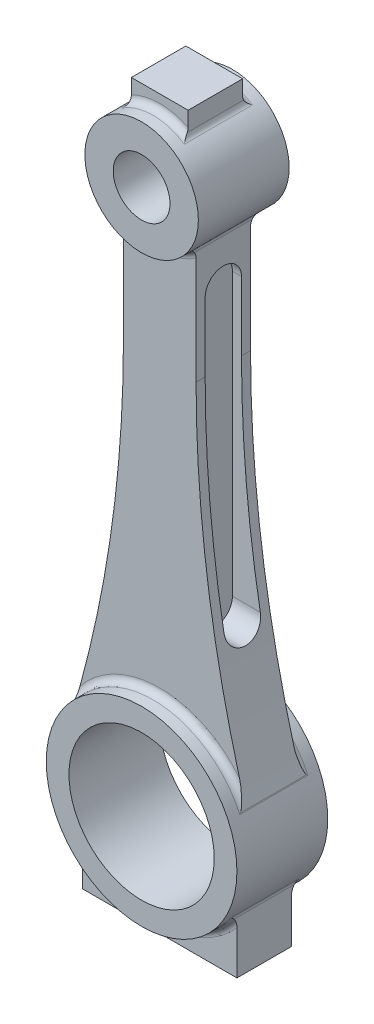
SolidWorks part; units mm, degrees
material "Ti-8Mn annealed sheet (SS)"
ref_plane "Front Plane" through (0, 0, 0) normal (0, 0, 1) x (1, 0, 0)
ref_plane "Top Plane" through (0, 0, 0) normal (0, 1, 0) x (1, 0, 0)
ref_plane "Right Plane" through (0, 0, 0) normal (1, 0, 0) x (0, 0, -1)
sketch "Sketch1" plane through (0, 0, 0) normal (0, 0, 1) x (1, 0, 0)
  circle A0 centre (0, 0) radius 16
  circle A1 centre (0, 0) radius 21
  circle A2 centre (0, 120) radius 6.25
  circle A3 centre (0, 120) radius 12.5
  point P7 (0, 0)
  dimension "D1" = 32
  dimension "D2" = 42
  dimension "D3" = 12.5
  dimension "D4" = 25
  dimension "D5" = 120
extrude "Boss-Extrude1" add sketch "Sketch1" along normal mid plane 20
sketch "Sketch2" plane through (0, 0, 0) normal (0, 0, 1) x (1, 0, 0)
  line L0 (0, 120) -> (0, 84.8343) construction
  line L1 (8, 110.3953) -> (8, 84.8343)
  line L2 (-8, 110.3953) -> (-8, 84.8343)
  circle A0 centre (0, 120) radius 12.5 construction
  arc A1 (8, 84.8343) -> (19.0917, 8.7467) centre (274.5199, 84.8343) ccw
  circle A2 centre (0, 0) radius 21 construction
  arc A3 (-8, 84.8343) -> (-19.0917, 8.7467) centre (-274.5199, 84.8343) cw
  arc A4 (19.0917, 8.7467) -> (-19.0917, 8.7467) centre (0, 0) ccw
  arc A5 (-8, 110.3953) -> (8, 110.3953) centre (0, 120) ccw
  point P6 (19.0917, 8.7467)
  point P10 (8.5229, 84.8343)
  point P17 (8, 84.8343)
  point P18 (8, 84.8343)
  dimension "D1" = 8
extrude "Boss-Extrude2" add sketch "Sketch2" along normal mid plane 12
sketch "Sketch4" plane through (0, 0, 0) normal (0, 0, 1) x (1, 0, 0)
  line L0 (0, 120) -> (0, 0) construction
  line L1 (17, -24.3288) -> (17, -12.3288)
  line L2 (-17, -24.3288) -> (-17, -12.3288)
  line L3 (-17, -24.3288) -> (17, -24.3288)
  line L4 (6.25, 135.8253) -> (6.25, 130.8253)
  line L5 (-6.25, 135.8253) -> (-6.25, 130.8253)
  line L6 (-6.25, 135.8253) -> (6.25, 135.8253)
  circle A0 centre (0, 0) radius 21 construction
  arc A1 (-17, -12.3288) -> (17, -12.3288) centre (0, 0) ccw
  circle A2 centre (0, 120) radius 12.5 construction
  arc A3 (6.25, 130.8253) -> (-6.25, 130.8253) centre (0, 120) ccw
  dimension "D1" = 34
  dimension "D2" = 12
  dimension "D3" = 12.5
  dimension "D4" = 5
extrude "Boss-Extrude3" add sketch "Sketch4" along normal mid plane 12
fillet "Fillet1" radius 1.5 16 edges at (0, 132.5, 6) (-6.25, 130.8253, 0) (-8, 110.3953, 0) (0, 107.5, 6) (0, 107.5, -6) (8, 110.3953, 0) (0, 132.5, -6) (6.25, 130.8253, 0) (0, 21, -6) (0, 21, 6) (-19.0917, 8.7467, 0) (0, -21, 6) (-17, -12.3288, 0) (0, -21, -6) (17, -12.3288, 0) (19.0917, 8.7467, 0)
ref_plane "Plane1" through (18, 0, 0) normal (1, 0, 0) x (0, 0, -1)
sketch "Sketch5" plane through (18, 0, 0) normal (1, 0, 0) x (0, 0, -1)
  line L0 (-10, 120) -> (10, 120) construction
  line L1 (-10, 132.5) -> (-10, 107.5) construction
  line L2 (10, 107.5) -> (10, 132.5) construction
  line L3 (0, 38) -> (0, 100) construction
  line L4 (-4, 38) -> (-4, 100)
  line L5 (4, 38) -> (4, 100)
  arc A0 (-4, 38) -> (4, 38) centre (0, 38) ccw
  arc A1 (4, 100) -> (-4, 100) centre (0, 100) ccw
  point P8 (0, 69)
  dimension "D3" = 4
  dimension "D1" = 20
  dimension "D2" = 62
extrude "Cut-Extrude1" cut sketch "Sketch5" against normal blind 12
mirror "Mirror1" about plane through (0, 0, 0) normal (1, 0, 0) of "Cut-Extrude1"
